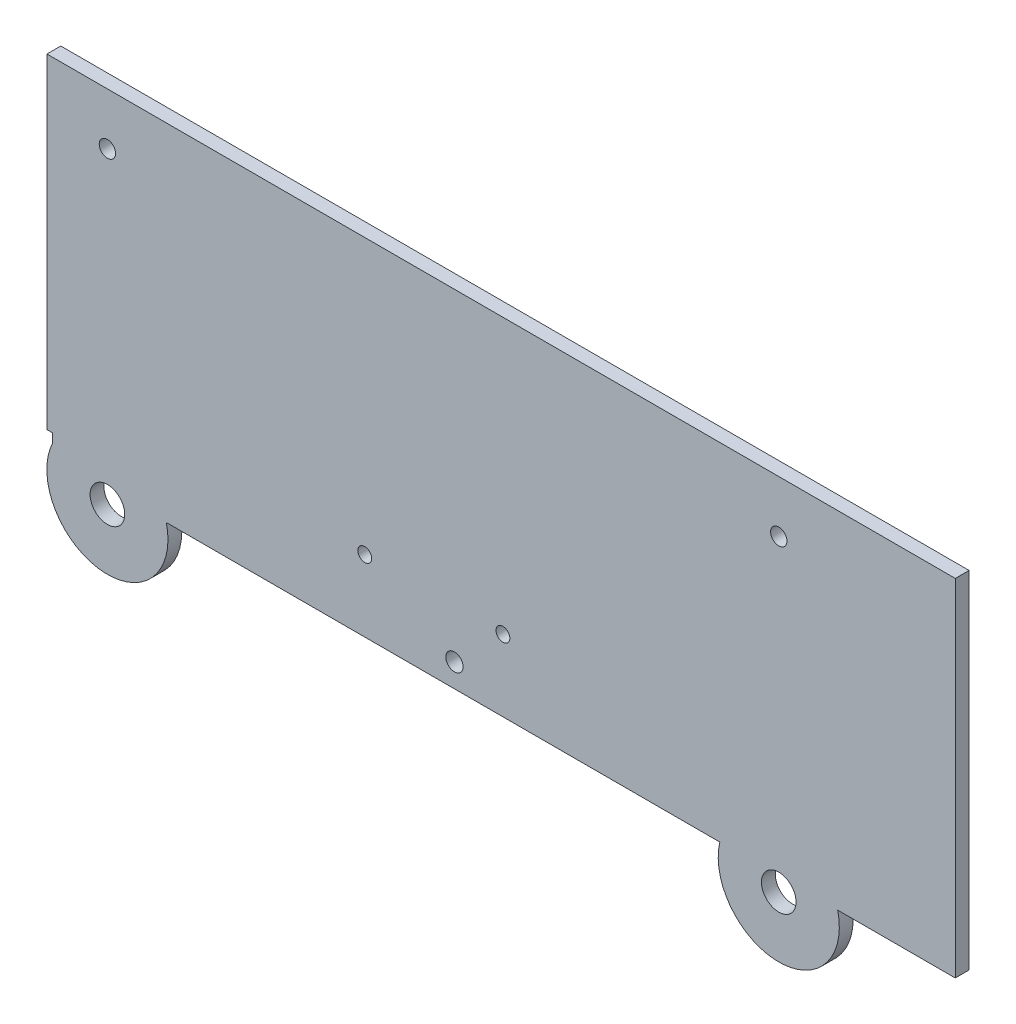
SolidWorks part; units mm, degrees
ref_plane "Front Plane" through (0, 0, 0) normal (0, 0, 1) x (1, 0, 0)
ref_plane "Top Plane" through (0, 0, 0) normal (0, 1, 0) x (1, 0, 0)
ref_plane "Right Plane" through (0, 0, 0) normal (1, 0, 0) x (0, 0, -1)
sketch "Sketch2" plane through (0, 0, 0) normal (0, 0, 1) x (1, 0, 0)
  line L1 (-143.383, -31.75) -> (143.383, -31.75)
  line L2 (-143.383, -31.75) -> (-143.383, 31.75)
  line L3 (-143.383, 31.75) -> (143.383, 31.75)
  line L4 (143.383, -31.75) -> (143.383, 31.75)
  line L5 (-143.383, -31.75) -> (143.383, 31.75) construction
  line L6 (-143.383, 31.75) -> (143.383, -31.75) construction
  line L16 (-143.383, 31.75) -> (143.383, 31.75)
  line L17 (-143.383, 31.75) -> (-143.383, 95.25)
  line L18 (-143.383, 95.25) -> (143.383, 95.25)
  line L19 (143.383, 31.75) -> (143.383, 95.25)
  circle A0 centre (-123.317, -36.83) radius 6.35
  circle A1 centre (123.063, -36.83) radius 6.35
  point P0 (0, 0)
  point P11 (0, 0)
  dimension "D3" = 20.066
  dimension "D5" = 5.08
  dimension "D7" = 63.5
  dimension "D1" = 63.5
  dimension "D2" = 286.766
  dimension "D6" = 20.32
extrude "Boss-Extrude1" add sketch "Sketch2" against normal blind 5.0749 contours A1 L1 L4 L3 L2 A0 | L3 L19 L18 L17 region at (0.0001, 0.0226, 0) region at (0, 63.5, 0)
ref_plane "Plane1" through (-143.383, 95.25, 0) normal (0, 1, 0) x (1, 0, 0)
ref_plane "Plane2" through (0, 0, -5.0749) normal (0, 0, -1) x (-1, 0, 0)
sketch "Sketch5" plane through (0, 0, -5.0749) normal (0, 0, -1) x (-1, 0, 0)
  line L5 (-143.383, -31.75) -> (-187.833, -31.75)
  line L6 (-143.383, -31.75) -> (-143.383, 95.25)
  line L7 (-143.383, 95.25) -> (-187.833, 95.25)
  line L8 (-187.833, -31.75) -> (-187.833, 95.25)
  dimension "D1" = 44.45
  dimension "D2" = 127
extrude "Boss-Extrude2" add sketch "Sketch5" against normal blind 5.0749
sketch "Sketch6" plane through (0, 0, -5.0749) normal (0, 0, -1) x (-1, 0, 0)
  line L0 (-116.713, -36.83) -> (-129.413, -36.83) construction
  line L1 (-123.063, -30.48) -> (-123.063, -43.18) construction
  line L3 (123.317, -30.48) -> (123.317, -43.18) construction
  line L4 (123.317, -43.18) -> (116.967, -36.83) construction
  line L6 (116.967, -36.83) -> (129.667, -36.83) construction
  circle A2 centre (-123.063, -36.83) radius 6.35 construction
  circle A3 centre (-123.063, -36.83) radius 22.225
  circle A4 centre (123.317, -36.83) radius 6.35 construction
  circle A5 centre (123.317, -36.83) radius 22.225
  dimension "D1" = 44.45
  dimension "D2" = 44.45
extrude "Boss-Extrude3" add sketch "Sketch6" against normal blind 5.0749
extrude "Cut-Extrude2" cut sketch "Sketch2<3>" against normal blind 5.588 contours A0 | A1
sketch "Sketch2<3>" plane through (0, 0, 0) normal (0, 0, 1) x (1, 0, 0) same geometry as "Sketch2"
sketch "Sketch8" plane through (0, 0, -5.0749) normal (0, 0, -1) x (-1, 0, 0)
  line L0 (145.5039, -24.13) -> (145.5039, 95.25) construction
  line L1 (198.383, 95.25) -> (88.383, 95.25) construction
  line L2 (143.383, -27.2746) -> (143.383, 95.25) construction
  line L4 (145.5039, 95.25) -> (142.7757, 95.25)
  line L5 (145.5039, 95.25) -> (145.5039, -24.13)
  line L6 (145.5039, -24.13) -> (142.7757, -24.13)
  line L7 (142.7757, 95.25) -> (142.7757, -24.13)
  dimension "D1" = 2.1209
extrude "Boss-Extrude4" add sketch "Sketch8" against normal blind 5.0749
sketch "Sketch9" plane through (0, 0, -5.0749) normal (0, 0, -1) x (-1, 0, 0)
  line L0 (-123.063, -43.18) -> (-123.063, 95.25) construction
  line L1 (145.5039, 95.25) -> (-187.833, 95.25) construction
  line L2 (-123.063, 95.25) -> (123.317, -43.18) construction
  line L3 (123.317, -43.18) -> (123.317, 95.25) construction
  line L4 (123.317, 95.25) -> (-123.063, -43.18) construction
  line L5 (-123.063, -43.18) -> (-123.063, 95.25) construction
  line L6 (-123.063, 95.25) -> (-123.063, 76.2) construction
  line L7 (-123.063, 76.2) -> (123.317, 76.2) construction
  circle A0 centre (-123.063, -36.83) radius 6.35 construction
  circle A1 centre (123.317, -36.83) radius 6.35 construction
  circle A2 centre (-123.063, 76.2) radius 3
  circle A3 centre (123.317, 76.2) radius 3
  dimension "D1" = 19.05
extrude "Cut-Extrude3" cut sketch "Sketch9" against normal blind 400.05
sketch "Sketch10" plane through (0, 0, -5.0749) normal (0, 0, -1) x (-1, 0, 0)
  line L0 (145.5039, -12.1559) -> (28.8696, -12.1559) construction
  line L1 (145.5039, -24.13) -> (145.5039, 95.25) construction
  line L2 (28.8696, -12.1559) -> (-21.8287, -12.1559) construction
  line L3 (-21.8287, -31.75) -> (-21.8287, -5.5256)
  line L4 (101.6804, -31.75) -> (-101.4264, -31.75) construction
  line L5 (28.8696, -31.75) -> (28.8696, -5.5256) construction
  line L6 (-11.6609, -31.75) -> (-11.6609, -23.1778) construction
  line L7 (-21.8287, -23.1778) -> (28.8696, -23.1778)
  circle A0 centre (-21.8287, -5.5256) radius 2.54
  circle A1 centre (28.8696, -5.5256) radius 2.54
  circle A2 centre (-4.0466, -23.1778) radius 3.175
extrude "Cut-Extrude4" cut sketch "Sketch10" against normal blind 6.35 contours A0 | A1 | A2 region at (23.5739, -3.7804, -5.0749) region at (-28.8696, -5.5256, -5.0749)
